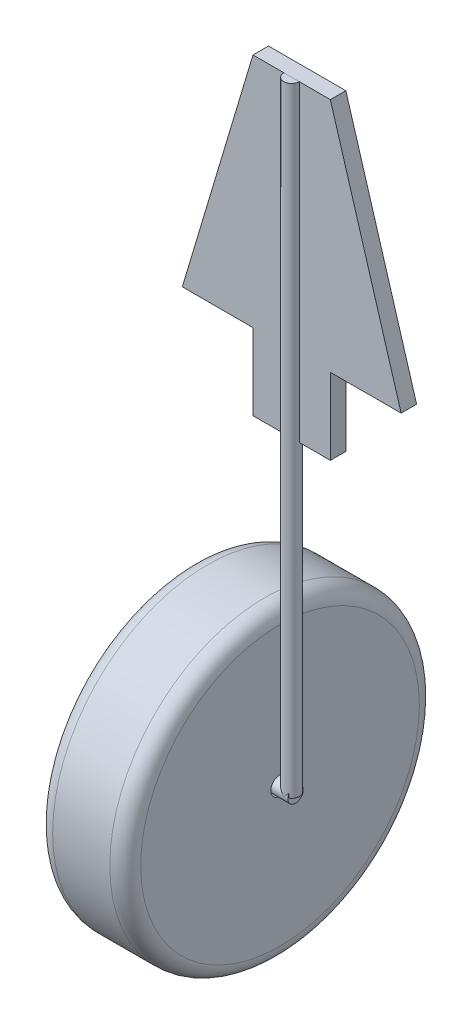
SolidWorks part; units mm, degrees
material "Silicon Rubber"
ref_plane "Front Plane" through (0, 0, 0) normal (0, 0, 1) x (1, 0, 0)
ref_plane "Top Plane" through (0, 0, 0) normal (0, 1, 0) x (1, 0, 0)
ref_plane "Right Plane" through (0, 0, 0) normal (1, 0, 0) x (0, 0, -1)
sketch "Sketch1" plane through (0, 0, 0) normal (1, 0, 0) x (0, 0, -1)
  circle A0 centre (0, 0) radius 10
  circle A1 centre (0, 0) radius 0.6
  dimension "D1" = 20
  dimension "D2" = 1.2
extrude "Boss-Extrude1" add sketch "Sketch1" along normal blind 5.69
fillet "Fillet2" radius 1 1 edges at (0, 0, -10)
fillet "Fillet3" radius 1 1 edges at (5.69, 0, -10)
sketch "Sketch2" plane through (5.69, 0, 0) normal (1, 0, 0) x (0, 0, -1)
  circle A0 centre (0, 0) radius 0.5
  dimension "D1" = 1
extrude "Boss-Extrude2" add sketch "Sketch2" along normal blind 1 and the other way blind 6 separate body
sketch "Sketch4" plane through (0, 0, 0) normal (0, 1, 0) x (1, 0, 0)
  line L0 (9.1493, 0) -> (0, 0) construction
  circle A0 centre (6.4348, 0) radius 0.5
  dimension "D1" = 1
extrude "Boss-Extrude5" add sketch "Sketch4" along normal blind 40
sketch "Sketch14" plane through (0, 0, 0) normal (0, 0, 1) x (1, 0, 0)
  line L5 (6.4348, 40) -> (6.4348, 5.6979) construction
  line L6 (6.9348, 40) -> (5.9348, 40) construction
  line L7 (8.9428, 40) -> (3.9428, 40)
  line L8 (3.9428, 19.814) -> (8.9428, 19.814)
  line L9 (8.9428, 19.814) -> (8.9428, 24.742)
  line L10 (8.9428, 24.742) -> (13.516, 24.742)
  line L11 (13.516, 24.742) -> (8.9428, 40)
  line L12 (3.9428, 19.814) -> (3.9428, 24.742)
  line L13 (3.9428, 24.742) -> (-0.6232, 24.742)
  line L14 (-0.6232, 24.742) -> (3.9428, 40)
  point P7 (6.4428, 40)
  dimension "D1" = 5
  dimension "D2" = 3.9428
  dimension "D3" = 19.814
  dimension "D4" = 13.516
  dimension "D5" = 0.6232
  dimension "D6" = 24.742
extrude "Boss-Extrude7" add sketch "Sketch14" along normal blind 0.001 and the other way blind 1 separate body
